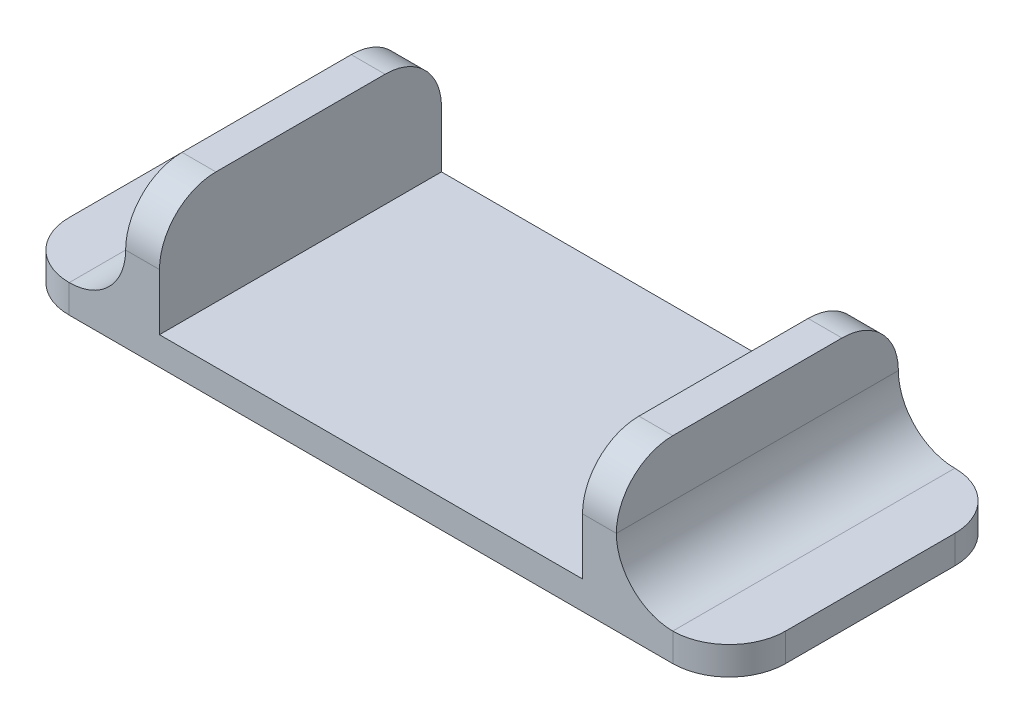
SolidWorks part; units mm, degrees
ref_plane "Front Plane" through (0, 0, 0) normal (0, 0, 1) x (1, 0, 0)
ref_plane "Top Plane" through (0, 0, 0) normal (0, 1, 0) x (1, 0, 0)
ref_plane "Right Plane" through (0, 0, 0) normal (1, 0, 0) x (0, 0, -1)
sketch "Sketch1" plane through (0, 0, 0) normal (0, 0, 1) x (1, 0, 0)
  line L0 (0, 0) -> (-77, 0)
  line L1 (-77, 0) -> (-77, 40)
  line L2 (0, 0) -> (0, 40)
  line L3 (-77, 40) -> (-82, 40)
  line L4 (0, 40) -> (5, 40)
  line L5 (-82, 40) -> (-82, 0)
  line L6 (5, 40) -> (5, 0)
  line L7 (-82, 0) -> (-102, 0)
  line L8 (5, 0) -> (25, 0)
  line L9 (25, 0) -> (25, -5)
  line L11 (-102, -5) -> (-102, 0)
  line L12 (25, -5) -> (-102, -5)
extrude "Boss-Extrude1" add sketch "Sketch1" along normal blind 50
fillet "Fillet1" radius 10 10 edges at (25, -2.5, 0) (25, -2.5, 50) (-102, -2.5, 0) (-102, -2.5, 50) (2.5, 40, 50) (2.5, 40, 0) (-79.5, 40, 0) (-79.5, 40, 50) (-82, 0, 25) (5, 0, 25)
sketch "Sketch2" plane through (-77, 0, 0) normal (1, 0, 0) x (0, 0, -1)
  line L4 (0, 0) -> (0, 30)
  line L5 (-10, 40) -> (-40, 40)
  line L6 (-50, 30) -> (-50, 0)
  line L7 (-50, 0) -> (0, 0)
  line L8 (0, 0) -> (0, 30)
  line L9 (-10, 40) -> (-40, 40)
  line L10 (-50, 30) -> (-50, 0)
  line L11 (-50, 0) -> (0, 0)
  arc A2 (0, 30) -> (-10, 40) centre (-10, 30) ccw
  arc A3 (-40, 40) -> (-50, 30) centre (-40, 30) ccw
  arc A4 (0, 30) -> (-10, 40) centre (-10, 30) ccw
  arc A5 (-40, 40) -> (-50, 30) centre (-40, 30) ccw
  dimension "D1" = 0
extrude "Boss-Extrude2" add sketch "Sketch2" along normal blind 1
sketch "Sketch3" plane through (0, 0, 0) normal (-1, 0, 0) x (0, 0, 1)
  line L4 (50, 0) -> (50, 30)
  line L5 (40, 40) -> (10, 40)
  line L6 (0, 30) -> (0, 0)
  line L7 (0, 0) -> (50, 0)
  line L8 (50, 0) -> (50, 30)
  line L9 (40, 40) -> (10, 40)
  line L10 (0, 30) -> (0, 0)
  line L11 (0, 0) -> (50, 0)
  arc A2 (50, 30) -> (40, 40) centre (40, 30) ccw
  arc A3 (10, 40) -> (0, 30) centre (10, 30) ccw
  arc A4 (50, 30) -> (40, 40) centre (40, 30) ccw
  arc A5 (10, 40) -> (0, 30) centre (10, 30) ccw
  dimension "D1" = 0
extrude "Boss-Extrude3" add sketch "Sketch3" along normal blind 1
sketch "Sketch4" plane through (0, 0, 50) normal (0, 0, 1) x (1, 0, 0)
  line L0 (5, 10) -> (5, 30) construction
  line L1 (-82, 40) -> (5, 40)
  line L2 (-82, 40) -> (-82, 20)
  line L3 (-82, 20) -> (5, 20)
  line L4 (5, 40) -> (5, 20)
extrude "Cut-Extrude1" cut sketch "Sketch4" against normal blind 93
fillet "Fillet2" radius 10 4 edges at (2, 20, 50) (2, 20, 0) (-79, 20, 0) (-79, 20, 50)
